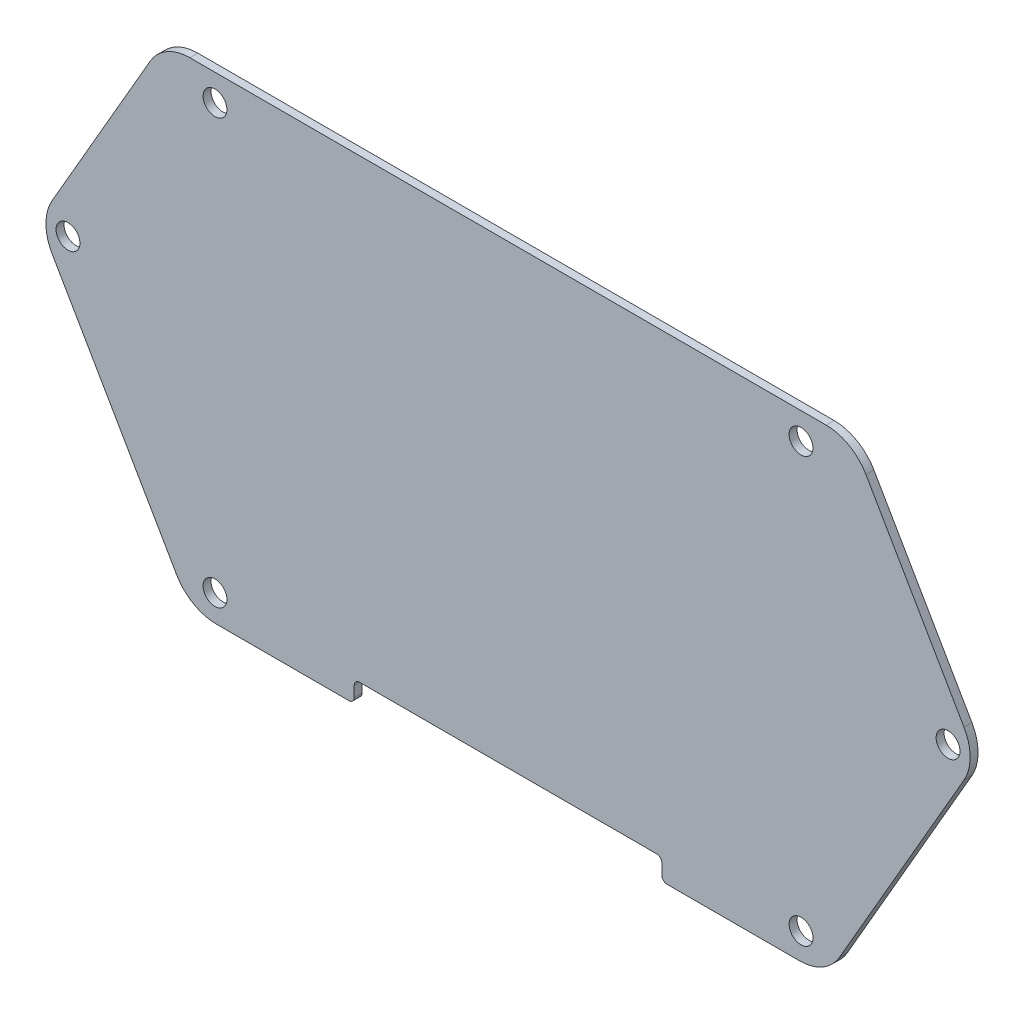
SolidWorks part; units mm, degrees
ref_plane "Plano frontal" through (0, 0, 0) normal (0, 0, 1) x (1, 0, 0)
ref_plane "Plano superior" through (0, 0, 0) normal (0, 1, 0) x (1, 0, 0)
ref_plane "Plano direito" through (0, 0, 0) normal (1, 0, 0) x (0, 0, -1)
sketch "Esboço2" plane through (0, 0, 0) normal (0, 0, 1) x (1, 0, 0)
  line L0 (60, -49.3301) -> (-60, -49.3301)
  line L5 (-60, -49.3301) -> (-88.4808, 0)
  line L6 (-88.4808, 0) -> (-65, 40.6699)
  line L7 (-65, 40.6699) -> (65, 40.6699)
  line L8 (65, 40.6699) -> (88.4808, 0)
  line L9 (88.4808, 0) -> (60, -49.3301)
  line L10 (-88.4808, 0) -> (88.4808, 0) construction
  line L11 (0, -49.3301) -> (0, 40.6699) construction
  point P15 (0, 40.6699)
  dimension "D1" = 90
  dimension "D2" = 130
  dimension "D3" = 120
  dimension "D4" = 60
  dimension "D7" = 60
base flange "Flange-base1" sketch "Esboço2" thickness 1.5 reverse thickness direction no parameters "D1"=0.7366
sketch "Esboço7" plane through (0, 0, -1.5) normal (0, 0, -1) x (-1, 0, 0)
  line L0 (0, 40.6699) -> (0, -49.3301) construction
  line L1 (-65, 40.6699) -> (65, 40.6699) construction
  line L2 (60, -49.3301) -> (-60, -49.3301) construction
  line L3 (88.4808, 0) -> (-88.4808, 0) construction
  line L4 (55.2577, -44.3301) -> (55.2577, 35.6699) construction
  line L5 (55.2577, 35.6699) -> (-55.2577, 35.6699) construction
  line L6 (-55.2577, 35.6699) -> (-55.2577, -44.3301) construction
  line L7 (-55.2577, -44.3301) -> (55.2577, -44.3301) construction
  line L8 (0, 35.6699) -> (0, 40.6699) construction
  line L9 (0, -44.3301) -> (0, -49.3301) construction
  line L10 (55.2577, -4.3301) -> (0, -4.3301) construction
  line L11 (0, -4.3301) -> (-55.2577, -4.3301) construction
  circle A0 centre (-82.9808, 0) radius 2.25
  circle A1 centre (-55.2577, -44.3301) radius 2.25
  circle A2 centre (55.2577, -44.3301) radius 2.25
  circle A3 centre (82.9808, 0) radius 2.25
  circle A4 centre (55.2577, 35.6699) radius 2.25
  circle A5 centre (-55.2577, 35.6699) radius 2.25
  point P36 (55.2577, -46.4952)
  dimension "D1" = 4.5
  dimension "D2" = 55.2577
  dimension "D3" = 5
  dimension "D4" = 5.5
  dimension "D5" = 5.5
extrude "Corte-extrusão1" cut sketch "Esboço7" against normal blind 10 normal cut yes
sketch "Esboço8" plane through (0, 0, 0) normal (0, 0, 1) x (1, 0, 0)
  line L0 (65, 40.6699) -> (-65, 40.6699) construction
  line L1 (-65, 40.6699) -> (-88.4808, 0) construction
  line L2 (-88.4808, 0) -> (-60, -49.3301) construction
  line L3 (-85.9808, -4.3301) -> (-62.5, -45)
  line L4 (-67.5, 36.3397) -> (-85.9808, 4.3301)
  line L5 (-60, -49.3301) -> (60, -49.3301) construction
  line L10 (-88.4808, 40.6699) -> (-60, 40.6699)
  line L11 (-88.4808, 40.6699) -> (-88.4808, -49.3301)
  line L12 (-88.4808, -49.3301) -> (-55, -49.3301)
  arc A0 (-67.5, 36.3397) -> (-60, 40.6699) centre (-60, 32.0096) cw
  arc A1 (-85.9808, -4.3301) -> (-85.9808, 4.3301) centre (-78.4808, 0) cw
  arc A2 (-62.5, -45) -> (-55, -49.3301) centre (-55, -40.6699) ccw
  dimension "D1" = 5
  dimension "D2" = 5
  dimension "D3" = 5
extrude "Corte-extrusão3" cut sketch "Esboço8" against normal blind 10 normal cut yes
mirror "Espelhar1" about plane through (0, 0, 0) normal (1, 0, 0) of "Corte-extrusão3"
sketch "Esboço9" plane through (0, 0, 0) normal (0, 0, 1) x (1, 0, 0)
  line L1 (-55, -49.3301) -> (55, -49.3301) construction
  line L2 (-29, -48.3301) -> (-29, -46.3301)
  line L3 (-28, -45.3301) -> (28, -45.3301)
  line L4 (0, 0) -> (0, -49.3301) construction
  line L5 (-30, -49.3301) -> (30, -49.3301)
  line L6 (29, -48.3301) -> (29, -46.3301)
  arc A0 (-30, -49.3301) -> (-29, -48.3301) centre (-30, -48.3301) ccw
  arc A1 (-29, -46.3301) -> (-28, -45.3301) centre (-28, -46.3301) cw
  arc A2 (29, -46.3301) -> (28, -45.3301) centre (28, -46.3301) ccw
  arc A3 (30, -49.3301) -> (29, -48.3301) centre (30, -48.3301) cw
  point P18 (0, -45.3301)
  dimension "D2" = 1
  dimension "D1" = 4
  dimension "D3" = 28
extrude "Corte-extrusão4" cut sketch "Esboço9" against normal blind 10 normal cut yes
sketch "Curva-Linhas1" [suppressed] plane through (0, 0, 0) normal (0, 1, 0) x (1, 0, 0)
sketch "Caixa delimitadora1" [suppressed] plane through (0, 0, 0) normal (0, 1, 0) x (1, 0, 0)
sheet metal parameters "Chapa metálica1" thickness 1.5 parameters "D1"=0.7366
flat pattern "Padrão-Plano1" [suppressed]
sketch "Curva-Linhas2" plane through (0, 0, 0) normal (0, 1, 0) x (1, 0, 0)
sketch3d "Caixa delimitadora2" [suppressed]
  line L0 (39.4797, -22.5812, 0) -> (-45.4615, -22.5812, 0) construction
  line L1 (39.4797, 23.1794, 0) -> (-45.4615, 23.1794, 0) construction
  line L2 (39.4797, -22.5812, 0) -> (39.4797, 23.1794, 0) construction
  line L3 (-45.4615, -22.5812, 0) -> (-45.4615, 23.1794, 0) construction
sheet metal parameters "Chapa metálica2" thickness 1.5 parameters "D1"=0.7366
flat pattern "Padrão-Plano1"
sketch "Curva-Linhas2" plane through (0, 0, 0) normal (0, 1, 0) x (1, 0, 0)
sketch3d "Caixa delimitadora2" [suppressed]
  line L0 (-88.4808, -49.3301, 0) -> (88.4808, -49.3301, 0) construction
  line L1 (-88.4808, 40.6699, 0) -> (88.4808, 40.6699, 0) construction
  line L2 (-88.4808, -49.3301, 0) -> (-88.4808, 40.6699, 0) construction
  line L3 (88.4808, -49.3301, 0) -> (88.4808, 40.6699, 0) construction
sheet metal parameters "Chapa metálica4" thickness 1.5 parameters "D1"=0.7366
flat pattern "Padrão-Plano1"
sketch "Curva-Linhas2" plane through (0, 0, 0) normal (0, 1, 0) x (1, 0, 0)
sketch3d "Caixa delimitadora2" [suppressed]
  line L0 (-87.1409, -49.3301, 0) -> (88.4808, -49.3301, 0) construction
  line L1 (-87.1409, 40.6699, 0) -> (88.4808, 40.6699, 0) construction
  line L2 (-87.1409, -49.3301, 0) -> (-87.1409, 40.6699, 0) construction
  line L3 (88.4808, -49.3301, 0) -> (88.4808, 40.6699, 0) construction
sheet metal parameters "Chapa metálica5" thickness 1.5 parameters "D1"=0.7366
flat pattern "Padrão-Plano1"
sketch "Curva-Linhas2" plane through (0, 0, 0) normal (0, 1, 0) x (1, 0, 0)
sketch3d "Caixa delimitadora2" [suppressed]
  line L0 (-87.1409, -49.3301, 0) -> (87.1409, -49.3301, 0) construction
  line L1 (-87.1409, 40.6699, 0) -> (87.1409, 40.6699, 0) construction
  line L2 (-87.1409, -49.3301, 0) -> (-87.1409, 40.6699, 0) construction
  line L3 (87.1409, -49.3301, 0) -> (87.1409, 40.6699, 0) construction
sheet metal parameters "Chapa metálica6" thickness 1.5 parameters "D1"=0.7366
flat pattern "Padrão-Plano1"
sketch "Curva-Linhas2" plane through (0, 0, 0) normal (0, 1, 0) x (1, 0, 0)
sketch3d "Caixa delimitadora2" [suppressed]
  line L0 (-87.1409, -49.3301, 0) -> (87.1409, -49.3301, 0) construction
  line L1 (-87.1409, 40.6699, 0) -> (87.1409, 40.6699, 0) construction
  line L2 (-87.1409, -49.3301, 0) -> (-87.1409, 40.6699, 0) construction
  line L3 (87.1409, -49.3301, 0) -> (87.1409, 40.6699, 0) construction
